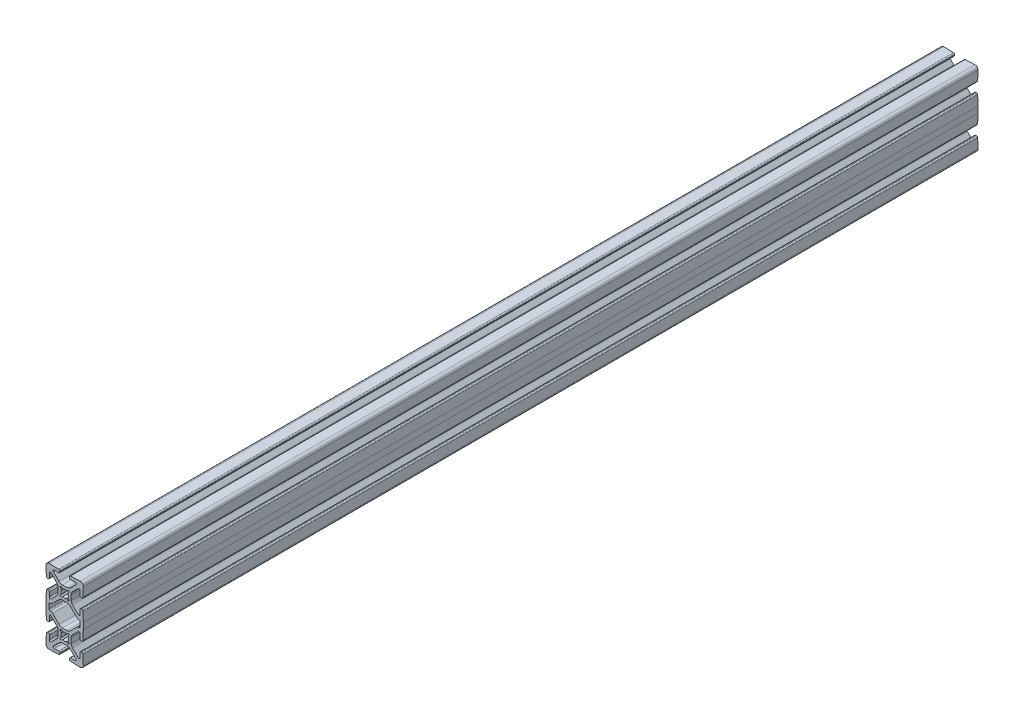
SolidWorks part; units mm, degrees
ref_plane "Front Plane" through (0, 0, 0) normal (0, 0, 1) x (1, 0, 0)
ref_plane "Top Plane" through (0, 0, 0) normal (0, 1, 0) x (1, 0, 0)
ref_plane "Right Plane" through (0, 0, 0) normal (1, 0, 0) x (0, 0, -1)
sketch "Sketch1" plane through (0, 0, 0) normal (0, 0, 1) x (1, 0, 0)
  line L0 (0, 12.5) -> (0, 25) construction
  line L1 (0, 12.5) -> (12.5, 12.5) construction
  line L2 (0, 12.5) -> (-12.5, 25) construction
  line L3 (-10.3971, 24.9988) -> (-3.9863, 24.7749)
  line L4 (-12.5, 25) -> (0, 25) construction
  line L5 (-3.2505, 23.9858) -> (-3.2689, 23.4569)
  line L6 (-4.058, 22.7211) -> (-6.948, 22.8221)
  line L10 (0, 16.88) -> (-1.5587, 16.88)
  line L11 (-3.8038, 17.8099) -> (-7.5141, 21.5202)
  line L24 (0, 12.5) -> (-12.5, 12.5) construction
  line L25 (-12.5, 12.5) -> (0, 12.5) construction
  line L26 (0, 12.5) -> (0, 0) construction
  line L27 (-12.5, 0) -> (-12.5, 25) construction
  line L28 (0, 25) -> (12.5, 25) construction
  line L29 (0, 0) -> (0, -25) construction
  line L30 (-12.5, -25) -> (12.5, -25) construction
  arc A0 (-11.9048, 24.4048) -> (-10.3971, 24.9988) centre (-10.468, 22.968) cw
  arc A4 (-3.2689, 23.4569) -> (-4.058, 22.7211) centre (-4.0314, 23.4836) cw
  arc A5 (-3.9863, 24.7749) -> (-3.2505, 23.9858) centre (-4.0129, 24.0125) cw
  arc A6 (-1.5587, 16.88) -> (-3.8038, 17.8099) centre (-1.5587, 20.055) cw
  circle A16 centre (0, 12.5) radius 2.55
  arc A18 (-7.5141, 21.5202) -> (-6.948, 22.8221) centre (-6.9746, 22.0596) cw
  circle A19 centre (-2.3794, 14.8794) radius 0.635 construction
  point P15 (0, 0)
  point P35 (-3.2956, 22.6945)
  point P38 (-3.2238, 24.7483)
  point P42 (-2.8739, 16.88)
  point P80 (-12.5, 12.5)
  point P85 (0, 0)
  point P88 (0, 0)
  dimension "D11" = 2.032
  dimension "D15" = 3.175
  dimension "Center Hole Diameter" = 5.1
  dimension "D6" = 1.27
  dimension "D1" = 45
  dimension "D2" = 2
  dimension "Rail Width" = 25
  dimension "D10" = 2.13
  dimension "T-Slot Depth" = 8.12
  dimension "D9" = 2.055
  dimension "Rail Height" = 50
  dimension "D23" = 8.76
  dimension "D5" = 15.475
  dimension "T-Slot Width" = 6.5
  dimension "D3" = 4
sketch "Sketch2" plane through (0, 0, 0) normal (1, 0, 0) x (0, 0, -1)
  line L0 (-300, 0) -> (300, 0)
  line L1 (-300, -25) -> (-300, 25) construction
  line L2 (0, 12.5) -> (0, 25) construction
  line L3 (0, 12.5) -> (0, 25) construction
  line L4 (300, -25) -> (300, 25) construction
  point P0 (-262.5, 0)
  point P3 (0, 0)
  point P7 (262.5, 0)
  point P11 (-300, 0)
  dimension "D1" = 37.5
  dimension "Representative Length" = 600
sketch "Sketch3" plane through (0, 0, 0) normal (0, 0, 1) x (1, 0, 0)
  line L1 (0, 12.5) -> (-12.5, 25) construction
  line L2 (0, 12.5) -> (-12.5, 25) construction
  line L3 (-4.38, 12.5) -> (-2.55, 12.5) construction
  line L4 (-4.38, 10.9413) -> (-4.38, 14.0587)
  line L5 (-10.3971, 24.9988) -> (-3.9863, 24.7749) construction
  line L6 (-3.2505, 23.9858) -> (-3.2689, 23.4569) construction
  line L7 (-4.058, 22.7211) -> (-6.948, 22.8221) construction
  line L12 (-5.3099, 16.3038) -> (-9.0202, 20.0141)
  line L13 (-10.2211, 16.558) -> (-10.3221, 19.448)
  line L14 (-11.4858, 15.7505) -> (-10.9569, 15.7689)
  line L15 (-12.4988, 22.8971) -> (-12.2749, 16.4863)
  line L16 (-2.8284, 14.4304) -> (-2.1953, 13.7973)
  line L17 (1.5587, 8.12) -> (-1.5587, 8.12)
  line L18 (-1.2973, 14.6953) -> (-1.9304, 15.3284)
  line L19 (-3.8038, 7.1901) -> (-8.1307, 2.8632)
  line L23 (-1.2973, 10.3047) -> (-1.9304, 9.6716)
  line L42 (-3.8038, 17.8099) -> (-7.5141, 21.5202) construction
  line L43 (0, 16.88) -> (-1.5587, 16.88) construction
  line L44 (-10.3971, 24.9988) -> (-3.9863, 24.7749)
  line L45 (-3.2505, 23.9858) -> (-3.2689, 23.4569)
  line L46 (-4.058, 22.7211) -> (-6.948, 22.8221)
  line L47 (-3.8038, 17.8099) -> (-7.5141, 21.5202)
  line L48 (1.5587, 16.88) -> (-1.5587, 16.88)
  line L59 (0, 16.88) -> (0, 15.05) construction
  line L60 (-2.8284, 10.5696) -> (-2.1953, 11.2027)
  line L61 (-12.5, 2.0675) -> (-12.2749, 8.5137)
  line L62 (-11.4858, 9.2495) -> (-10.9569, 9.2311)
  line L63 (-10.2211, 8.442) -> (-10.3221, 5.552)
  line L64 (-5.3099, 8.6962) -> (-9.0202, 4.9859)
  line L66 (10.468, 0) -> (-10.468, 0) construction
  line L67 (-10.468, 0) -> (-10.468, 1.506)
  line L68 (-9.706, 2.268) -> (-9.5675, 2.268)
  line L71 (-12.5, 0) -> (-12.5, 2.0675)
  line L72 (-12.5, 0) -> (-12.5, 25) construction
  line L76 (-12.5, 0) -> (-10.468, 0)
  line L78 (4.38, 12.5) -> (2.55, 12.5) construction
  line L79 (12.5, 0) -> (10.468, 0)
  line L80 (12.5, 0) -> (12.5, 2.0675)
  line L81 (9.706, 2.268) -> (9.5675, 2.268)
  line L82 (10.468, 0) -> (10.468, 1.506)
  line L83 (5.3099, 8.6962) -> (9.0202, 4.9859)
  line L84 (10.2211, 8.442) -> (10.3221, 5.552)
  line L85 (11.4858, 9.2495) -> (10.9569, 9.2311)
  line L86 (12.5, 2.0675) -> (12.2749, 8.5137)
  line L87 (2.8284, 10.5696) -> (2.1953, 11.2027)
  line L89 (3.8038, 17.8099) -> (7.5141, 21.5202)
  line L90 (4.058, 22.7211) -> (6.948, 22.8221)
  line L91 (3.2505, 23.9858) -> (3.2689, 23.4569)
  line L92 (10.3971, 24.9988) -> (3.9863, 24.7749)
  line L93 (1.2973, 10.3047) -> (1.9304, 9.6716)
  line L94 (3.8038, 7.1901) -> (8.1307, 2.8632)
  line L95 (1.2973, 14.6953) -> (1.9304, 15.3284)
  line L97 (2.8284, 14.4304) -> (2.1953, 13.7973)
  line L98 (12.4988, 22.8971) -> (12.2749, 16.4863)
  line L99 (11.4858, 15.7505) -> (10.9569, 15.7689)
  line L100 (10.2211, 16.558) -> (10.3221, 19.448)
  line L101 (5.3099, 16.3038) -> (9.0202, 20.0141)
  line L102 (4.38, 10.9413) -> (4.38, 14.0587)
  line L103 (0, 12.5) -> (0, 25) construction
  arc A0 (-10.3971, 24.9988) -> (-11.9048, 24.4048) centre (-10.468, 22.968) ccw construction
  arc A1 (-3.8038, 7.1901) -> (-1.5587, 8.12) centre (-1.5587, 4.945) cw
  circle A3 centre (0, 12.5) radius 2.55
  arc A5 (-10.3971, 24.9988) -> (-12.4988, 22.8971) centre (-10.468, 22.968) ccw
  arc A6 (-5.3099, 16.3038) -> (-4.38, 14.0587) centre (-7.555, 14.0587) cw
  arc A7 (-10.3221, 19.448) -> (-9.0202, 20.0141) centre (-9.5596, 19.4746) cw
  arc A8 (-10.2211, 16.558) -> (-10.9569, 15.7689) centre (-10.9836, 16.5314) cw
  arc A9 (-11.4858, 15.7505) -> (-12.2749, 16.4863) centre (-11.5125, 16.5129) cw
  circle A10 centre (-2.3794, 14.8794) radius 0.635 construction
  arc A11 (-1.9304, 15.3284) -> (-2.8284, 14.4304) centre (-2.3794, 14.8794) ccw
  arc A12 (-2.1953, 13.7973) -> (-2.1953, 11.2027) centre (0, 12.5) ccw
  arc A16 (1.2973, 10.3047) -> (-1.2973, 10.3047) centre (0, 12.5) cw
  arc A17 (-1.9304, 9.6716) -> (-2.8284, 10.5696) centre (-2.3794, 10.1206) cw
  arc A18 (-11.4858, 9.2495) -> (-12.2749, 8.5137) centre (-11.5125, 8.4871) ccw
  arc A35 (1.2973, 14.6953) -> (-1.2973, 14.6953) centre (0, 12.5) ccw
  arc A36 (-3.2505, 23.9858) -> (-3.9863, 24.7749) centre (-4.0129, 24.0125) ccw construction
  arc A37 (-4.058, 22.7211) -> (-3.2689, 23.4569) centre (-4.0314, 23.4836) ccw construction
  arc A38 (-6.948, 22.8221) -> (-7.5141, 21.5202) centre (-6.9746, 22.0596) ccw construction
  arc A39 (-3.8038, 17.8099) -> (-1.5587, 16.88) centre (-1.5587, 20.055) ccw construction
  arc A41 (-3.2505, 23.9858) -> (-3.9863, 24.7749) centre (-4.0129, 24.0125) ccw
  arc A42 (-4.058, 22.7211) -> (-3.2689, 23.4569) centre (-4.0314, 23.4836) ccw
  arc A43 (-6.948, 22.8221) -> (-7.5141, 21.5202) centre (-6.9746, 22.0596) ccw
  arc A44 (-3.8038, 17.8099) -> (-1.5587, 16.88) centre (-1.5587, 20.055) ccw
  arc A52 (-10.2211, 8.442) -> (-10.9569, 9.2311) centre (-10.9836, 8.4686) ccw
  arc A53 (-10.3221, 5.552) -> (-9.0202, 4.9859) centre (-9.5596, 5.5254) ccw
  arc A54 (-5.3099, 8.6962) -> (-4.38, 10.9413) centre (-7.555, 10.9413) ccw
  arc A55 (-10.468, 1.506) -> (-9.706, 2.268) centre (-9.706, 1.506) cw
  arc A56 (-9.5675, 2.268) -> (-8.1307, 2.8632) centre (-9.5675, 4.3) ccw
  circle A57 centre (0, 12.5) radius 2.55 construction
  arc A58 (9.5675, 2.268) -> (8.1307, 2.8632) centre (9.5675, 4.3) cw
  arc A59 (10.468, 1.506) -> (9.706, 2.268) centre (9.706, 1.506) ccw
  arc A60 (5.3099, 8.6962) -> (4.38, 10.9413) centre (7.555, 10.9413) cw
  arc A61 (10.3221, 5.552) -> (9.0202, 4.9859) centre (9.5596, 5.5254) cw
  arc A62 (10.2211, 8.442) -> (10.9569, 9.2311) centre (10.9836, 8.4686) cw
  arc A63 (3.8038, 17.8099) -> (1.5587, 16.88) centre (1.5587, 20.055) cw
  arc A64 (6.948, 22.8221) -> (7.5141, 21.5202) centre (6.9746, 22.0596) cw
  arc A65 (4.058, 22.7211) -> (3.2689, 23.4569) centre (4.0314, 23.4836) cw
  arc A66 (3.2505, 23.9858) -> (3.9863, 24.7749) centre (4.0129, 24.0125) cw
  arc A68 (11.4858, 9.2495) -> (12.2749, 8.5137) centre (11.5125, 8.4871) cw
  arc A69 (1.9304, 9.6716) -> (2.8284, 10.5696) centre (2.3794, 10.1206) ccw
  arc A71 (2.1953, 13.7973) -> (2.1953, 11.2027) centre (0, 12.5) cw
  arc A72 (1.9304, 15.3284) -> (2.8284, 14.4304) centre (2.3794, 14.8794) cw
  arc A73 (11.4858, 15.7505) -> (12.2749, 16.4863) centre (11.5125, 16.5129) ccw
  arc A74 (10.2211, 16.558) -> (10.9569, 15.7689) centre (10.9836, 16.5314) ccw
  arc A75 (10.3221, 19.448) -> (9.0202, 20.0141) centre (9.5596, 19.4746) ccw
  arc A76 (5.3099, 16.3038) -> (4.38, 14.0587) centre (7.555, 14.0587) ccw
  arc A77 (10.3971, 24.9988) -> (12.4988, 22.8971) centre (10.468, 22.968) cw
  arc A78 (3.8038, 7.1901) -> (1.5587, 8.12) centre (1.5587, 4.945) ccw
  point P40 (0, 0)
  dimension "D3" = 2.032
  dimension "D4" = 0.762
  dimension "D5" = 2.032
  dimension "D2" = 4.536
  dimension "D1" = 0
extrude "Boss-Extrude1" add sketch "Sketch3" along normal mid plane 600
pattern_circular "CirPattern1" count 2 over 360 about axis through (0, 0, 300) along (0, 0, -1) of "Boss-Extrude1"
ref_plane "Contact Plane 1" through (0, 25, 0) normal (0, 1, 0) x (1, 0, 0)
ref_plane "Contact Plane 2" through (12.5, 12.5, 0) normal (1, 0, 0) x (0, 0, -1)
ref_plane "Contact Plane 3" through (0, -25, 0) normal (0, -1, 0) x (-1, 0, 0)
ref_plane "Contact Plane 4" through (-12.5, 12.5, 0) normal (-1, 0, 0) x (0, 0, 1)
equation "\"D1@Sketch2\"=\"Rail Width@Sketch1\"*1.5"
equation "\"D1@Boss-Extrude1\" = \"Representative Length@Sketch2\""
